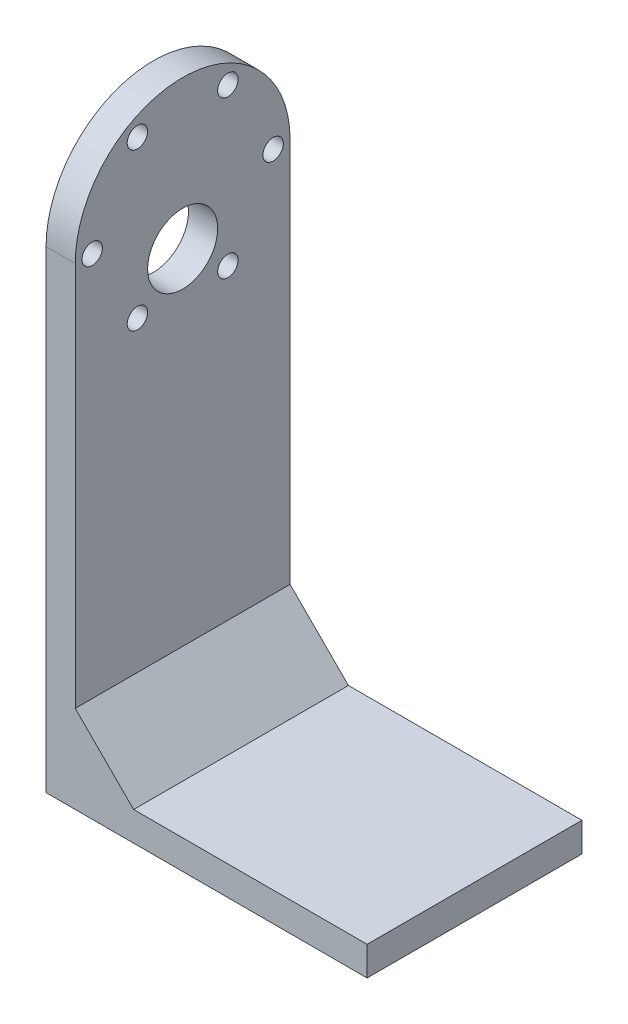
SolidWorks part; units mm, degrees
ref_plane "Płaszczyzna przednia" through (0, 0, 0) normal (0, 0, 1) x (1, 0, 0)
ref_plane "Płaszczyzna górna" through (0, 0, 0) normal (0, 1, 0) x (1, 0, 0)
ref_plane "Płaszczyzna prawa" through (0, 0, 0) normal (1, 0, 0) x (0, 0, -1)
sketch "Szkic1" plane through (752.6084, 0, 0) normal (-1, 0, 0) x (0, 0, 1)
  line L1 (1130.0601, -2000) -> (1407.0601, -2000) construction
  line L2 (1104.0601, -1919) -> (1104.0601, -2000)
  line L3 (1140.8601, -1919) -> (1140.8601, -2000)
  line L4 (1102.0601, -2000) -> (1407.0601, -2000)
  line L5 (1102.0601, -2023) -> (1102.0601, -1998) construction
  circle A0 centre (1114.7101, -1932.4234) radius 1.75 construction
  circle A1 centre (1122.4601, -1919) radius 18.4
  arc A2 (1140.8601, -1919) -> (1104.0601, -1919) centre (1122.4601, -1919) ccw
  circle A3 centre (1130.2101, -1932.4234) radius 1.75 construction
  circle A4 centre (1137.9601, -1919) radius 1.75 construction
  circle A5 centre (1130.2101, -1905.5766) radius 1.75 construction
  circle A6 centre (1114.7101, -1905.5766) radius 1.75 construction
  circle A7 centre (1106.9601, -1919) radius 1.75 construction
  circle A8 centre (1114.7101, -1932.4234) radius 1.75
  circle A9 centre (1130.2101, -1932.4234) radius 1.75
  circle A10 centre (1137.9601, -1919) radius 1.75
  circle A11 centre (1130.2101, -1905.5766) radius 1.75
  circle A12 centre (1114.7101, -1905.5766) radius 1.75
  circle A13 centre (1106.9601, -1919) radius 1.75
  arc M2 (1113.2348, -1927.2857) -> (1131.6854, -1927.2857) centre (1122.4601, -1919) cw
  arc M4 (1130.9082, -1926.9376) -> (1114.012, -1926.9376) centre (1122.4601, -1926) ccw
  circle M6 centre (1135.8835, -1926.75) radius 1.9
  circle M7 centre (1109.0367, -1926.75) radius 1.9
  circle M8 centre (1122.4601, -1903.5) radius 1.9
  circle M15 centre (1122.4601, -1926) radius 6
  circle M16 centre (1122.4601, -1919) radius 18.4
  dimension "D1" = 0
extrude "Dodanie-wyciągnięcie1" add sketch "Szkic1" along normal blind 5 contours L3 L2 M16 | A13 A12 A11 A10 A9 A8 M16 M7 M15 M8 M6 M2 M4 | M2 M4 | M7 | M6 | M8 region at (752.6084, -1966.5989, 1122.4601) region at (752.6084, -1918.0781, 1122.4601) region at (752.6084, -1926.75, 1135.8835) region at (752.6084, -1926.75, 1109.0367) region at (752.6084, -1903.5, 1122.4601)
sketch "Szkic2" plane through (752.6084, 0, 0) normal (-1, 0, 0) x (0, 0, 1)
  line L0 (1140.8601, -1919) -> (1140.8601, -2000) construction
  line L1 (1104.0601, -2000) -> (1140.8601, -2000)
  line L2 (1104.0601, -2000) -> (1104.0601, -1995)
  line L3 (1104.0601, -1995) -> (1140.8601, -1995)
  line L4 (1140.8601, -2000) -> (1140.8601, -1995)
  line L5 (1122.4601, -1995) -> (1122.4601, -2000) construction
  line L6 (1104.0601, -1997.5) -> (1140.8601, -1997.5) construction
  point P88 (1122.4601, -1997.5)
  dimension "D1" = 5
extrude "Dodanie-wyciągnięcie2" add sketch "Szkic2" against normal blind 50
chamfer "Sfazowanie1" distance 10 angle 45 1 edges at (752.6084, -1995, 1122.4601)
